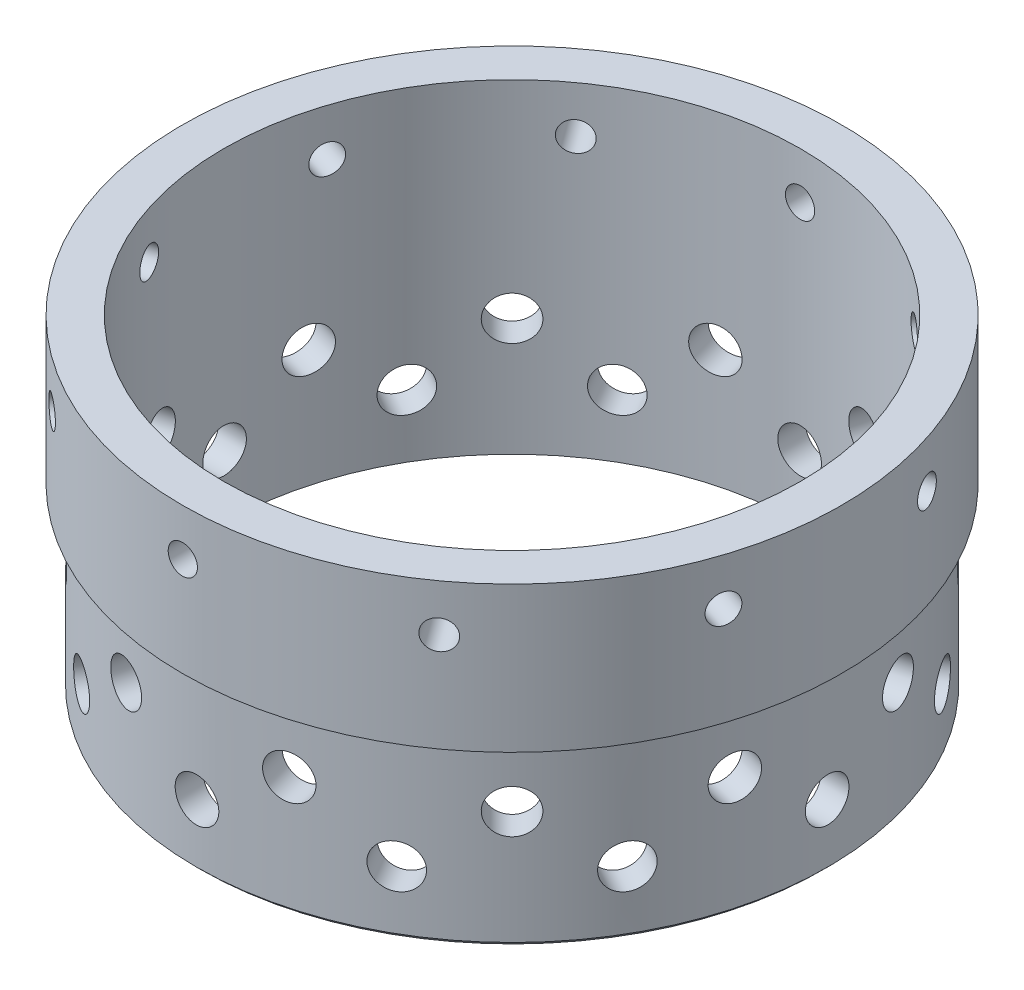
SolidWorks part; units mm, degrees
material "6061-T6 (SS)"
ref_plane "Front Plane" through (0, 0, 0) normal (0, 0, 1) x (1, 0, 0)
ref_plane "Top Plane" through (0, 0, 0) normal (0, 1, 0) x (1, 0, 0)
ref_plane "Right Plane" through (0, 0, 0) normal (1, 0, 0) x (0, 0, -1)
sketch "Sketch1" plane through (0, 0, 0) normal (0, 1, 0) x (1, 0, 0)
  circle A0 centre (0, 0) radius 66.5988
  circle A1 centre (0, 0) radius 76.1238
  circle A2 centre (0, 0) radius 72.9488
  dimension "D1" = 152.2476
  dimension "D2" = 3.175
  dimension "D3" = 6.35
  dimension "D4" = 9.525
  dimension "D5" = 145.8976
extrude "Boss-Extrude1" add sketch "Sketch1" along normal blind 12.7 contours A2 A0 | A1 A2 region at (-73.9707, 0, 0) region at (-70.8855, 0, 0)
extrude "Boss-Extrude2" add sketch "Sketch1<3>" against normal blind 41.275 contours A2 A0 region at (-70.8855, 0, 0)
sketch "Sketch1<3>" plane through (0, 0, 0) normal (0, 1, 0) x (1, 0, 0) same geometry as "Sketch1"
extrude "Boss-Extrude3" add sketch "Sketch1<4>" along normal blind 33.655 contours A2 A0 | A1 A2 region at (-73.9707, 0, 0) region at (-70.8855, 0, 0)
sketch "Sketch1<4>" plane through (0, 0, 0) normal (0, 1, 0) x (1, 0, 0) same geometry as "Sketch1"
chamfer "Chamfer1" distance 1 angle 45 1 edges at (0, -41.275, 72.9488)
sketch "Sketch2" plane through (0, 0, 0) normal (0, 0, 1) x (1, 0, 0)
  line L0 (0, 0) -> (0, 22.86) construction
  line L1 (0, 0) -> (0, -26.797) construction
  line L2 (-71.9488, -41.275) -> (71.9488, -41.275) construction
  line L4 (76.1238, 33.655) -> (-76.1238, 33.655) construction
  circle A0 centre (0, 22.86) radius 3.3782
  circle A1 centre (0, -26.797) radius 5.0419
  dimension "D1" = 6.7564
  dimension "D2" = 10.0838
  dimension "D3" = 26.797
  dimension "D5" = 14.478
  dimension "D4" = 10.795
extrude "Cut-Extrude1" cut sketch "Sketch2" against normal through all contours A1 region at (0, -26.797, 0)
ref_plane "Plane1" through (-19.7023, 0, 73.5299) normal (-0.2588, 0, 0.9659) x (0, -1, 0)
sketch "Sketch3" plane through (-19.7023, 0, 73.5299) normal (-0.2588, 0, 0.9659) x (0, -1, 0)
  line L0 (14.097, 0) -> (0, 0) construction
  line L1 (41.275, -71.9488) -> (41.275, 71.9488) construction
  circle A0 centre (14.097, 0) radius 5.0419
  dimension "D1" = 10.0838
  dimension "D2" = 14.097
  dimension "D3" = 27.178
extrude "Cut-Extrude2" cut sketch "Sketch3" against normal blind 38.1
pattern_circular "CirPattern2" count 12 over 360 about axis through (0, 12.7, 0) along (0, -1, 0) of "Cut-Extrude2", "Cut-Extrude1" reverse direction yes
extrude "Cut-Extrude3" cut sketch "Sketch2<3>" against normal through all contours A0
sketch "Sketch2<3>" plane through (0, 0, 0) normal (0, 0, 1) x (1, 0, 0) same geometry as "Sketch2"
pattern_circular "CirPattern3" count 10 over 360 about axis through (0, 12.7, 0) along (0, -1, 0) of "Cut-Extrude3"
fillet "Fillet1" radius 0.4064 1 edges at (0, 0, 72.9488)
equation "\"holeDia\"= 0.397in"
equation "\"D2@Sketch2\"=\"holeDia\""
equation "\"numHoles\"=12"
equation "\"D1@Plane1\"=180/\"numHoles\""
equation "\"D1@Sketch3\"=\"holeDia\""
equation "\"D1@CirPattern2\"=\"numHoles\""
